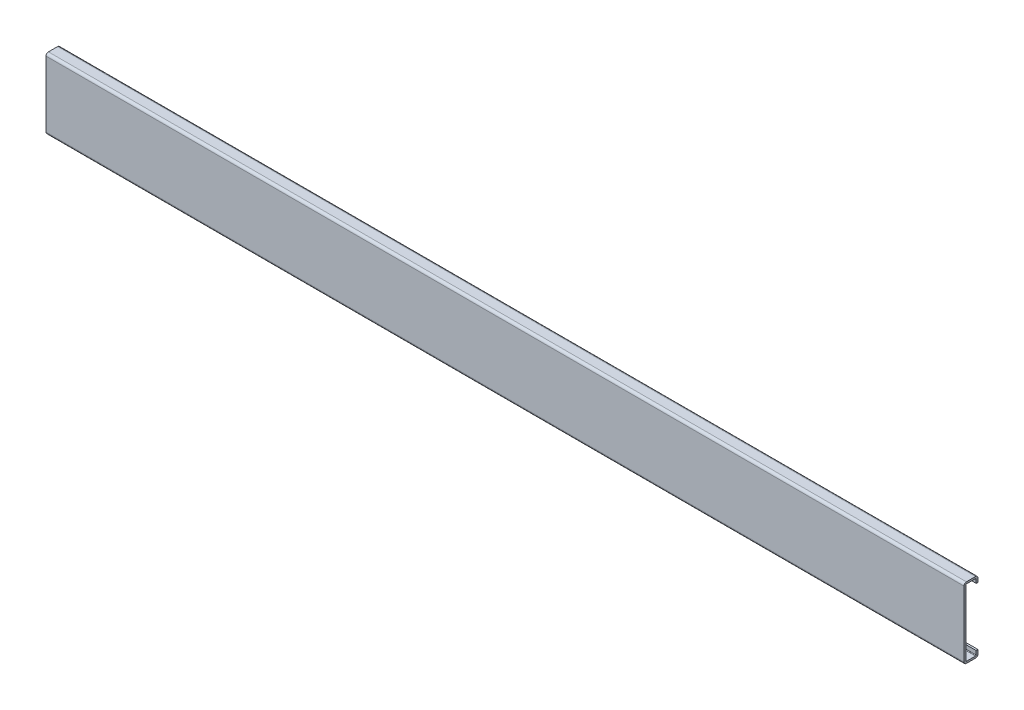
SolidWorks part; units mm, degrees
ref_plane "Спереди" through (0, 0, 0) normal (0, 0, 1) x (1, 0, 0)
ref_plane "Сверху" through (0, 0, 0) normal (0, 1, 0) x (1, 0, 0)
ref_plane "Справа" through (0, 0, 0) normal (1, 0, 0) x (0, 0, -1)
sketch "Эскиз1" plane through (0, 0, 0) normal (1, 0, 0) x (0, 0, -1)
  line L0 (0, -21.5) -> (0, 21.5)
  line L1 (-12.4481, 0) -> (26.4522, 0) construction
  line L2 (1, 22.5) -> (7, 22.5)
  line L3 (8, 21.5) -> (8, 19)
  line L4 (8, -21.5) -> (8, -19)
  line L5 (1, -22.5) -> (7, -22.5)
  arc A0 (7, 22.5) -> (8, 21.5) centre (7, 21.5) cw
  arc A1 (0, 21.5) -> (1, 22.5) centre (1, 21.5) cw
  arc A2 (0, -21.5) -> (1, -22.5) centre (1, -21.5) ccw
  arc A3 (7, -22.5) -> (8, -21.5) centre (7, -21.5) ccw
  point P0 (0, 0)
  point P19 (0, 0)
  dimension "D1" = 1
extrude "Вытянуть-Тонкостенный1" add sketch "Эскиз1" along normal blind 600 thin thin type mid plane wall 1.2
